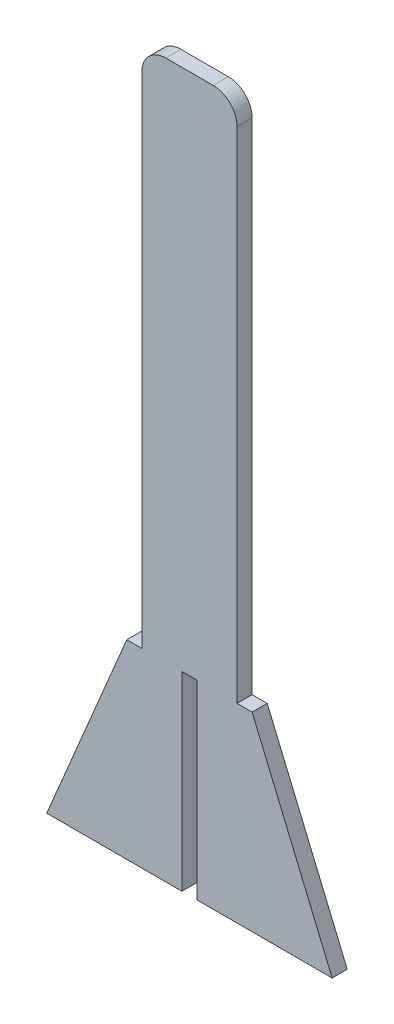
SolidWorks part; units mm, degrees
material "ABS"
ref_plane "Plan de face" through (0, 0, 0) normal (0, 0, 1) x (1, 0, 0)
ref_plane "Plan de dessus" through (0, 0, 0) normal (0, 1, 0) x (1, 0, 0)
ref_plane "Plan de droite" through (0, 0, 0) normal (1, 0, 0) x (0, 0, -1)
sketch "Esquisse1" plane through (0, 0, 0) normal (0, 0, 1) x (1, 0, 0)
  line L1 (-20, 300) -> (20, 300)
  line L2 (-20, 300) -> (-20, 80)
  line L4 (20, 300) -> (20, 80)
  line L8 (-60, 0) -> (60, 0)
  line L9 (26.35, 80) -> (-26.35, 80) construction
  line L10 (26.35, 80) -> (60, 0)
  line L11 (-26.35, 80) -> (-60, 0)
  line L12 (26.35, 80) -> (20, 80)
  line L13 (-20, 80) -> (-26.35, 80)
  point P1 (0, 0)
  point P2 (0, 300)
  point P8 (0, 80)
  dimension "D1" = 80
  dimension "D2" = 120
  dimension "D3" = 40
  dimension "D4" = 300
  dimension "D5" = 6.35
extrude "Boss.-Extru.1" add sketch "Esquisse1" along normal blind 6.35
fillet "Congé1" radius 10 2 edges at (-20, 300, 3.175) (20, 300, 3.175)
sketch "Esquisse2" plane through (0, 0, 6.35) normal (0, 0, 1) x (1, 0, 0)
  line L0 (-60, 0) -> (60, 0) construction
  line L1 (-3.175, 80) -> (3.175, 80)
  line L2 (-3.175, 80) -> (-3.175, 0)
  line L3 (-3.175, 0) -> (3.175, 0)
  line L4 (3.175, 80) -> (3.175, 0)
  line L5 (0, -3.4925) -> (0, 3.4925) construction
  point P8 (0, 80)
  dimension "D1" = 6.35
  dimension "D2" = 80
extrude "Enlèv. mat.-Extru.1" cut sketch "Esquisse2" against normal up to surface (6.35 mm away) up to face at (0, 150.4142, 0)
